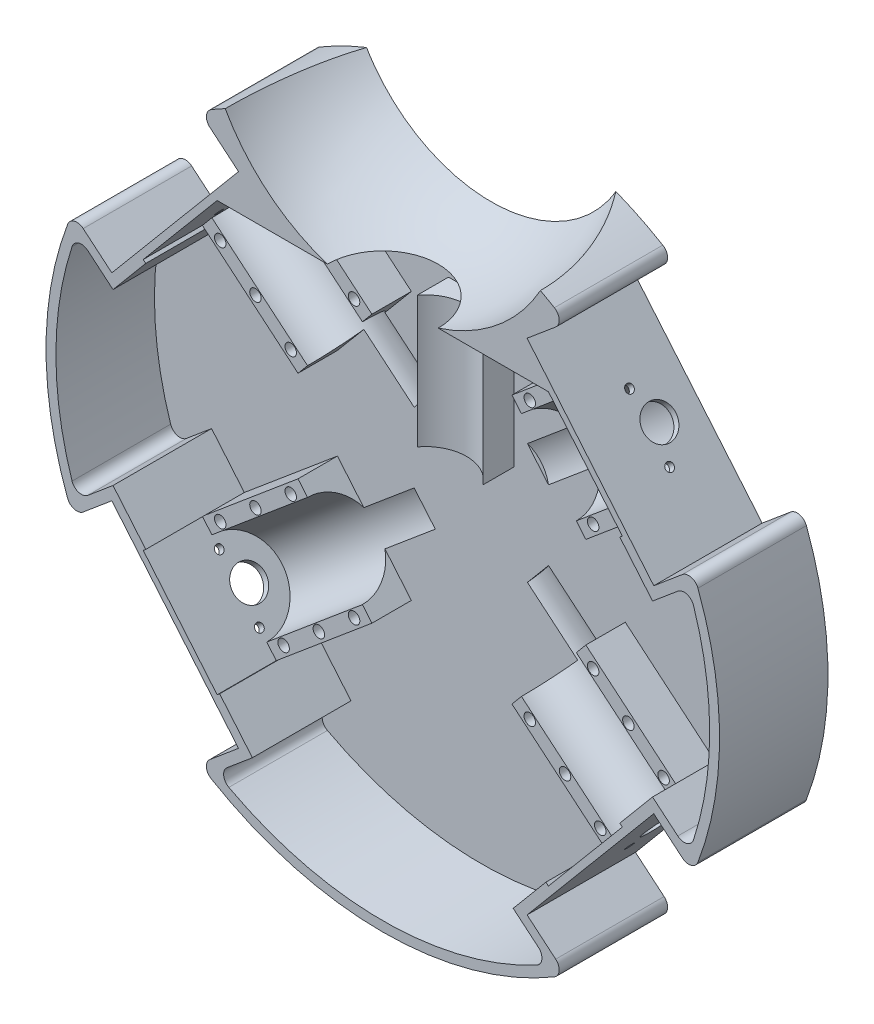
SolidWorks part; units mm, degrees
ref_plane "Front Plane" through (0, 0, 0) normal (0, 0, 1) x (1, 0, 0)
ref_plane "Top Plane" through (0, 0, 0) normal (0, 1, 0) x (1, 0, 0)
ref_plane "Right Plane" through (0, 0, 0) normal (1, 0, 0) x (0, 0, -1)
sketch "Sketch1" plane through (0, 0, 0) normal (0, 0, 1) x (1, 0, 0)
  circle A0 centre (0, 0) radius 102.5
  dimension "D1" = 205
extrude "Boss-Extrude1" add sketch "Sketch1" along normal blind 3
sketch "Sketch2" plane through (0, 0, 3) normal (0, 0, 1) x (1, 0, 0)
  line L0 (78.5196, 65.8857) -> (0, 0) construction
  line L1 (0, 0) -> (102.5, 0) construction
  line L2 (74.5568, 101.7228) -> (113.1241, 55.7601)
  line L3 (74.5568, 101.7228) -> (43.915, 76.0113)
  line L4 (113.1241, 55.7601) -> (82.4823, 30.0486)
  line L5 (43.915, 76.0113) -> (82.4823, 30.0486)
  line L6 (74.5568, 101.7228) -> (82.4823, 30.0486) construction
  line L7 (113.1241, 55.7601) -> (43.915, 76.0113) construction
  circle A0 centre (0, 0) radius 102.5 construction
  dimension "D1" = 40
  dimension "D2" = 60
  dimension "D3" = 40
extrude "Cut-Extrude1" cut sketch "Sketch2" against normal blind 3
sketch "Sketch3" plane through (0, 0, 3) normal (0, 0, 1) x (1, 0, 0)
  line L0 (51.9499, 66.4358) -> (74.4474, 39.6242)
  line L1 (51.9499, 66.4358) -> (21.3081, 40.7243)
  line L2 (74.4474, 39.6242) -> (43.8057, 13.9127)
  line L3 (21.3081, 40.7243) -> (43.8057, 13.9127)
  line L4 (43.915, 76.0113) -> (82.4823, 30.0486) construction
  point P6 (63.1987, 53.03)
  dimension "D1" = 35
  dimension "D2" = 40
extrude "Boss-Extrude2" add sketch "Sketch3" along normal blind 12
sketch "Sketch4" plane through (63.1987, 53.03, 0) normal (0.766, 0.6428, 0) x (0, 0, -1)
  line L0 (-15, -17.5) -> (-15, 17.5) construction
  circle A0 centre (-15, 0) radius 13
  dimension "D1" = 26
extrude "Cut-Extrude2" cut sketch "Sketch4" against normal blind 60
sketch "Sketch5" plane through (0, 0, 15) normal (0, 0, 1) x (1, 0, 0)
  line L0 (26.7453, 42.0231) -> (48.1945, 60.0211) construction
  line L1 (26.7453, 42.0231) -> (46.0289, 19.0417) construction
  line L2 (48.1945, 60.0211) -> (67.4782, 37.0398) construction
  line L3 (46.0289, 19.0417) -> (67.4782, 37.0398) construction
  line L4 (51.9499, 66.4358) -> (21.3081, 40.7243) construction
  line L5 (71.5549, 43.0714) -> (54.8424, 62.9886) construction
  line L6 (21.3081, 40.7243) -> (29.343, 31.1487) construction
  line L7 (57.8364, 48.5305) -> (63.1987, 53.03) construction
  circle A0 centre (26.7453, 42.0231) radius 1.75
  circle A1 centre (37.4699, 51.0221) radius 1.75
  circle A2 centre (48.1945, 60.0211) radius 1.75
  circle A3 centre (67.4782, 37.0398) radius 1.75
  circle A4 centre (56.7535, 28.0408) radius 1.75
  circle A5 centre (46.0289, 19.0417) radius 1.75
  dimension "D4" = 3.5
  dimension "D1" = 7
  dimension "D2" = 5
  dimension "D3" = 30
extrude "Cut-Extrude3" cut sketch "Sketch5" against normal through all
sketch "Sketch6" plane through (0, 0, 3) normal (0, 0, 1) x (1, 0, 0)
  line L0 (51.9499, 66.4358) -> (74.4474, 39.6242)
  line L1 (51.9499, 66.4358) -> (50.4178, 65.1502)
  line L2 (74.4474, 39.6242) -> (72.9154, 38.3386)
  line L3 (50.4178, 65.1502) -> (72.9154, 38.3386)
  dimension "D1" = 2
extrude "Boss-Extrude3" add sketch "Sketch6" along normal blind 30 and the other way blind 3
sketch "Sketch7" plane through (63.1987, 53.03, 0) normal (0.766, 0.6428, 0) x (0, 0, -1)
  line L0 (-15, 17.5) -> (-15, -17.5) construction
  line L1 (-33, 17.5) -> (-3, 17.5) construction
  line L2 (-33, -17.5) -> (-3, -17.5) construction
  line L3 (-15, 0) -> (-12, 0) construction
  line L4 (-3, 30) -> (-3, 17.5) construction
  circle A0 centre (-12, 0) radius 5
  circle A1 centre (-15, 9.5) radius 1.25
  circle A2 centre (-15, -9.5) radius 1.25
  dimension "D2" = 10
  dimension "D6" = 2.5
  dimension "D1" = 12
  dimension "D3" = 3
  dimension "D4" = 9.5
  dimension "D5" = 9.5
extrude "Cut-Extrude4" cut sketch "Sketch7" against normal blind 2
mirror "Mirror1" about plane through (0, 0, 0) normal (1, 0, 0) of "Cut-Extrude4", "Boss-Extrude3", "Cut-Extrude3", "Cut-Extrude2", "Boss-Extrude2", "Cut-Extrude1" second plane through (0, 0, 0) second plane normal (0, 1, 0)
sketch "Sketch8" plane through (0, 0, 3) normal (0, 0, 1) x (1, 0, 0)
  line L0 (74.4474, 39.6242) -> (82.4823, 30.0486) construction
  line L1 (82.4823, 30.0486) -> (94.3648, 40.0192) construction
  line L2 (82.4823, -30.0486) -> (94.3648, -40.0192) construction
  line L3 (74.4474, -39.6242) -> (82.4823, -30.0486) construction
  line L4 (43.915, -76.0113) -> (51.9499, -66.4358) construction
  line L5 (55.7975, -85.9819) -> (43.915, -76.0113) construction
  line L6 (-55.7975, -85.9819) -> (-43.915, -76.0113) construction
  line L7 (-43.915, -76.0113) -> (-51.9499, -66.4358) construction
  line L8 (-74.4474, 39.6242) -> (-82.4823, 30.0486) construction
  line L9 (-82.4823, 30.0486) -> (-94.3648, 40.0192) construction
  line L10 (-74.4474, -39.6242) -> (-82.4823, -30.0486) construction
  line L11 (-82.4823, -30.0486) -> (-94.3648, -40.0192) construction
  line L12 (74.4474, 39.6242) -> (82.4823, 30.0486)
  line L13 (82.4823, 30.0486) -> (94.3648, 40.0192)
  line L14 (82.4823, -30.0486) -> (94.3648, -40.0192)
  line L15 (74.4474, -39.6242) -> (82.4823, -30.0486)
  line L16 (43.915, -76.0113) -> (51.9499, -66.4358)
  line L17 (55.7975, -85.9819) -> (43.915, -76.0113)
  line L18 (-55.7975, -85.9819) -> (-43.915, -76.0113)
  line L19 (-43.915, -76.0113) -> (-51.9499, -66.4358)
  line L20 (-74.4474, 39.6242) -> (-82.4823, 30.0486)
  line L21 (-82.4823, 30.0486) -> (-94.3648, 40.0192)
  line L22 (-74.4474, -39.6242) -> (-82.4823, -30.0486)
  line L23 (-82.4823, -30.0486) -> (-94.3648, -40.0192)
  line L24 (72.1493, 37.6958) -> (82.1125, 25.8221)
  line L25 (82.1125, 25.8221) -> (93.1192, 35.0579)
  line L26 (82.1125, -25.8221) -> (93.1192, -35.0579)
  line L27 (72.1493, -37.6958) -> (82.1125, -25.8221)
  line L28 (-39.6885, -76.3811) -> (-49.6518, -64.5074)
  line L29 (-50.6953, -85.6168) -> (-39.6885, -76.3811)
  line L30 (50.6953, -85.6168) -> (39.6885, -76.3811)
  line L31 (39.6885, -76.3811) -> (49.6518, -64.5074)
  line L32 (-72.1493, 37.6958) -> (-82.1125, 25.8221)
  line L33 (-82.1125, 25.8221) -> (-93.1192, 35.0579)
  line L34 (-82.1125, -25.8221) -> (-93.1192, -35.0579)
  line L35 (-72.1493, -37.6958) -> (-82.1125, -25.8221)
  line L36 (-74.4474, 39.6242) -> (-72.1493, 37.6958)
  line L37 (-74.4474, -39.6242) -> (-72.1493, -37.6958)
  line L38 (-51.9499, -66.4358) -> (-49.6518, -64.5074)
  line L39 (49.6518, -64.5074) -> (51.9499, -66.4358)
  line L40 (72.1493, -37.6958) -> (74.4474, -39.6242)
  line L41 (72.1493, 37.6958) -> (74.4474, 39.6242)
  arc A0 (94.3648, -40.0192) -> (94.3648, 40.0192) centre (0, 0) ccw construction
  arc A1 (-55.7975, -85.9819) -> (55.7975, -85.9819) centre (0, 0) ccw construction
  arc A2 (-94.3648, 40.0192) -> (-94.3648, -40.0192) centre (0, 0) ccw construction
  arc A3 (94.3648, -40.0192) -> (94.3648, 40.0192) centre (0, 0) ccw
  arc A4 (-55.7975, -85.9819) -> (55.7975, -85.9819) centre (0, 0) ccw
  arc A5 (-94.3648, 40.0192) -> (-94.3648, -40.0192) centre (0, 0) ccw
  arc A6 (93.1192, -35.0579) -> (93.1192, 35.0579) centre (0, 0) ccw
  arc A7 (-50.6953, -85.6168) -> (50.6953, -85.6168) centre (0, 0) ccw
  arc A8 (-93.1192, 35.0579) -> (-93.1192, -35.0579) centre (0, 0) ccw
  dimension "D1" = 3
  dimension "D2" = 3
extrude "Boss-Extrude4" add sketch "Sketch8" along normal blind 30
sketch "Sketch9" plane through (0, 0, 3) normal (0, 0, 1) x (1, 0, 0)
  line L0 (43.915, 76.0113) -> (51.9499, 66.4358) construction
  line L1 (-43.915, 76.0113) -> (-51.9499, 66.4358) construction
  line L2 (55.7975, 85.9819) -> (43.915, 76.0113) construction
  line L3 (-55.7975, 85.9819) -> (-43.915, 76.0113) construction
  line L4 (43.915, 76.0113) -> (51.9499, 66.4358)
  line L5 (-43.915, 76.0113) -> (-51.9499, 66.4358)
  line L6 (55.7975, 85.9819) -> (43.915, 76.0113)
  line L7 (-55.7975, 85.9819) -> (-43.915, 76.0113)
  line L9 (-51.9499, 66.4358) -> (-50.4178, 65.1502)
  line L10 (-50.4178, 65.1502) -> (50.4178, 65.1502)
  line L11 (50.4178, 65.1502) -> (51.9499, 66.4358)
  arc A0 (55.7975, 85.9819) -> (-55.7975, 85.9819) centre (0, 0) ccw construction
  arc A1 (55.7975, 85.9819) -> (-55.7975, 85.9819) centre (0, 0) ccw
extrude "Boss-Extrude6" add sketch "Sketch9" along normal blind 30
sketch "Sketch10" plane through (0, 0, 33) normal (0, 0, 1) x (1, 0, 0)
  line L0 (-55, 117.5) -> (55, 117.5)
  line L1 (0, 117.5) -> (0, 102.5) construction
  arc A1 (-55, 117.5) -> (55, 117.5) centre (0, 117.5) ccw
  arc A2 (55.7975, 85.9819) -> (-55.7975, 85.9819) centre (0, 0) ccw construction
  dimension "D1" = 110
  dimension "D2" = 15
revolve "Cut-Revolve1" cut sketch "Sketch10" angle 360 about L0
fillet "Fillet1" radius 3 14 edges at (-50.6953, -85.6168, 18) (-93.1192, -35.0579, 18) (-93.1192, 35.0579, 18) (-94.3648, 40.0192, 16.5) (-94.3648, -40.0192, 16.5) (-55.7975, -85.9819, 16.5) (50.6953, -85.6168, 18) (55.7975, -85.9819, 16.5) (93.1192, -35.0579, 18) (94.3648, -40.0192, 16.5) (93.1192, 35.0579, 18) (94.3648, 40.0192, 16.5) (-55.7975, 85.9819, 16.5) (55.7975, 85.9819, 16.5)
sketch "Sketch11" plane through (0, 0, 3) normal (0, 0, 1) x (1, 0, 0)
  line L0 (0, 30.1502) -> (0, 0) construction
  line L1 (-10, 50.1502) -> (10, 50.1502)
  line L2 (-10, 50.1502) -> (-10, 10.1502)
  line L3 (-10, 10.1502) -> (10, 10.1502)
  line L4 (10, 50.1502) -> (10, 10.1502)
  line L5 (-10, 50.1502) -> (10, 10.1502) construction
  line L6 (-10, 10.1502) -> (10, 50.1502) construction
  line L7 (16.867, 65.1502) -> (50.4178, 65.1502) construction
  point P0 (0, 30.1502)
  dimension "D1" = 15
  dimension "D2" = 40
  dimension "D3" = 20
extrude "Boss-Extrude7" add sketch "Sketch11" along normal blind 10
sketch "Sketch12" plane through (0, 50.1502, 0) normal (0, 1, 0) x (1, 0, 0)
  line L0 (0, 0) -> (0, -20) construction
  circle A0 centre (0, -20) radius 12.5
  dimension "D1" = 25
  dimension "D2" = 20
extrude "Cut-Extrude5" cut sketch "Sketch12" against normal up to surface (40 mm away) up to face at (0, 10.1502, 8)
